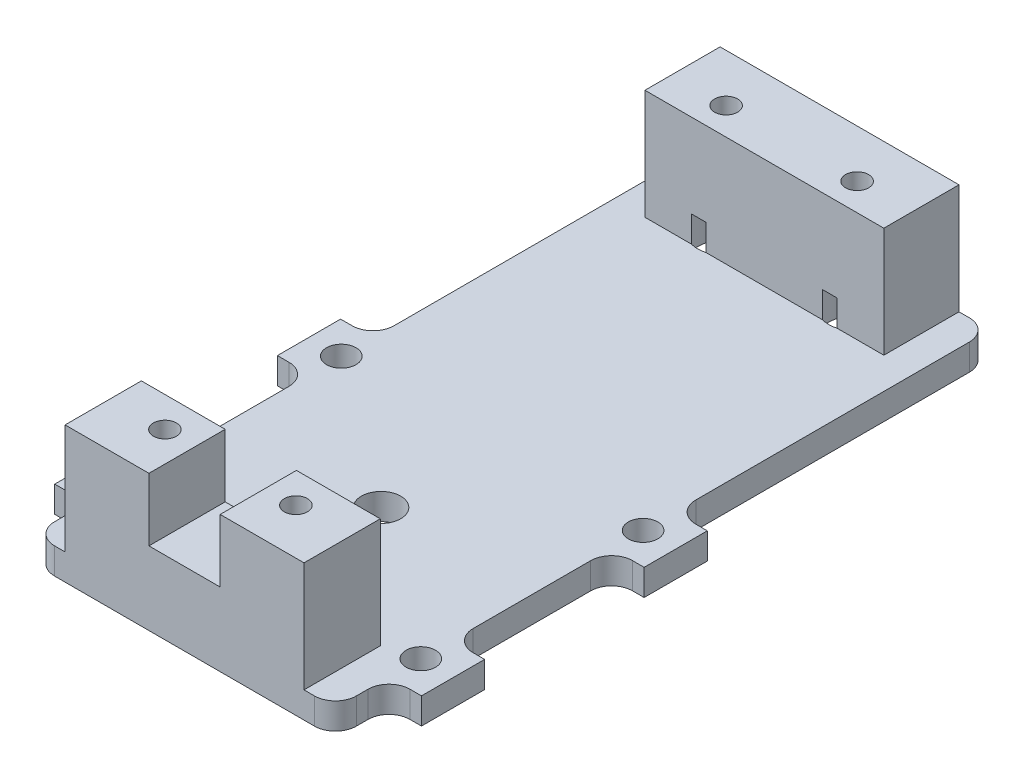
SolidWorks part; units mm, degrees
material "ABS"
ref_plane "Front Plane" through (0, 0, 0) normal (0, 0, 1) x (1, 0, 0)
ref_plane "Top Plane" through (0, 0, 0) normal (0, 1, 0) x (1, 0, 0)
ref_plane "Right Plane" through (0, 0, 0) normal (1, 0, 0) x (0, 0, -1)
sketch "Sketch1" plane through (0, 0, 0) normal (0, 1, 0) x (1, 0, 0)
  line L0 (18.288, -9.6647) -> (22.225, -9.6647)
  line L1 (-18.288, -23.8125) -> (18.288, -23.8125)
  line L2 (-18.288, -23.8125) -> (-18.288, -17.3228)
  line L3 (-18.288, 55.5625) -> (18.288, 55.5625)
  line L4 (18.288, -23.8125) -> (18.288, -17.3228)
  line L5 (-22.225, -17.3228) -> (-18.288, -17.3228)
  line L6 (-22.225, -17.3228) -> (-22.225, -9.6647)
  line L7 (-22.225, 17.3228) -> (-18.288, 17.3228)
  line L8 (22.225, -17.3228) -> (22.225, -9.6647)
  line L9 (0, 0.0043) -> (-31.7584, 0.0043) construction
  line L10 (-31.7584, 0.0043) -> (-18.288, -13.4661) construction
  line L11 (-22.225, -9.6647) -> (-18.288, -9.6647)
  line L12 (-18.288, 17.3228) -> (-18.288, 55.5625)
  line L13 (-22.225, 9.6647) -> (-18.288, 9.6647)
  line L14 (-18.288, -9.6647) -> (-18.288, 9.6647)
  line L15 (18.288, 9.6647) -> (22.225, 9.6647)
  line L17 (18.288, -9.6647) -> (18.288, 9.6647)
  line L18 (22.225, 9.6647) -> (22.225, 17.3228)
  line L19 (-22.225, 9.6647) -> (-22.225, 17.3228)
  line L20 (-18.288, -9.6647) -> (-18.288, 9.6647)
  line L21 (18.288, -9.6647) -> (18.288, 9.6647)
  line L22 (18.288, 17.3228) -> (18.288, 55.5625)
  line L23 (18.288, 17.3228) -> (22.225, 17.3228)
  line L24 (18.288, -17.3228) -> (22.225, -17.3228)
  line L25 (-31.7584, 0.0043) -> (-18.288, 13.4747) construction
  line L26 (0, -23.8125) -> (0, 0.0043) construction
  line L28 (-14.478, -13.8906) -> (14.478, -13.8906) construction
  line L29 (-14.478, -13.8906) -> (-14.478, 45.7994) construction
  line L30 (-14.478, 45.7994) -> (14.478, 45.7994) construction
  line L31 (14.478, -13.8906) -> (14.478, 45.7994) construction
  circle A0 centre (0, 0.0043) radius 2.3813
  circle A1 centre (7.9375, 49.7649) radius 3.429 construction
  circle A2 centre (-7.9375, 49.7649) radius 3.429 construction
  circle A3 centre (7.9375, -18.2563) radius 3.429 construction
  circle A4 centre (-7.9375, -18.2563) radius 3.429 construction
  point P4 (-7.9375, -18.2562)
  point P6 (0, 0)
  point P9 (7.9375, -18.2562)
  point P10 (-7.9375, 49.7649)
  point P11 (7.9375, 49.7649)
  point P31 (18.288, -13.4661)
  point P32 (18.288, 13.4747)
  dimension "D21" = 6.858
  dimension "D1" = 36.576
  dimension "D2" = 79.375
  dimension "D3" = 18.288
  dimension "D4" = 23.8125
  dimension "D5" = 18.2562
  dimension "D6" = 7.9375
  dimension "D9" = 5.5563
  dimension "D10" = 34.6456
  dimension "D11" = 44.45
  dimension "D12" = 19.3294
  dimension "D13" = 9.6647
  dimension "D14" = 19.05
  dimension "D15" = 19.05
  dimension "D16" = 90
  dimension "D17" = 28.956
  dimension "D18" = 14.478
  dimension "D19" = 59.69
  dimension "D20" = 13.8906
  dimension "D7" = 2
  dimension "D8" = 2
extrude "Boss-Extrude1" add sketch "Sketch1" along normal blind 3.175 contours L4 L24 L8 L0 L17 L15 L18 L23 L22 L3 L12 L7 L19 L13 L14 L11 L6 L5 L2 L1 L31 L28 L29 L30 region at (0, 0, -15.3322)
hole_wizard "9/64 (0.14063) Diameter Hole1" positions "Sketch5" profile "Sketch6" hole size "9/64" standard "Ansi Inch" end condition up to next
sketch "Sketch5" plane through (0, 0, 0) normal (0, -1, 0) x (1, 0, 0)
  point P4 (18.288, -13.4747)
  point P7 (18.288, 13.4661)
  point P35 (-18.288, -13.4704)
  point P37 (-18.288, 13.4704)
sketch "Sketch6" plane through (18.288, 0, -13.4747) normal (1, 0, 0) x (0, 0, -1)
  line L0 (0, 0) -> (0, 3.175)
  line L1 (0, 3.175) -> (1.786, 3.175)
  line L2 (1.786, 3.175) -> (1.786, 0)
  line L5 (1.786, 0) -> (0, 0)
  line L11 (0, -6.35) -> (0, 107.95) construction
  dimension "Thru Hole Dia." = 3.572
  dimension "Thru Hole Depth" = 3.175
fillet "Fillet1" radius 2.54 12 edges at (18.288, 1.5875, 23.8125) (18.288, 1.5875, 17.3228) (18.288, 1.5875, 9.6647) (18.288, 1.5875, -9.6647) (18.288, 1.5875, -17.3228) (18.288, 1.5875, -55.5625) (-18.288, 1.5875, -55.5625) (-18.288, 1.5875, -17.3228) (-18.288, 1.5875, -9.6647) (-18.288, 1.5875, 9.6647) (-18.288, 1.5875, 17.3228) (-18.288, 1.5875, 23.8125)
sketch "Sketch9" plane through (0, 0, 0) normal (0, 1, 0) x (1, 0, 0)
  line L0 (-18.288, 55.5625) -> (18.288, 55.5625) construction
  line L1 (-18.288, -23.8125) -> (18.288, -23.8125) construction
  line L5 (-14.478, -14.5696) -> (14.478, -14.5696)
  line L6 (-14.478, -14.5696) -> (-14.478, -23.8125)
  line L8 (-14.4653, 46.453) -> (14.4907, 46.453)
  line L9 (-14.4653, 46.453) -> (-14.4653, 55.5625)
  line L10 (-14.4653, 55.5625) -> (14.4907, 55.5625)
  line L11 (14.4907, 46.453) -> (14.4907, 55.5625)
  line L12 (-14.478, -23.8125) -> (14.478, -23.8125)
  line L13 (14.478, -14.5696) -> (14.478, -23.8125)
  circle A2 centre (-7.9375, -18.2562) radius 1.397
  circle A3 centre (7.9375, -18.2562) radius 1.397
  circle A4 centre (-7.9375, 49.7649) radius 1.397
  circle A5 centre (7.9375, 49.7649) radius 1.397
  dimension "D1" = 2.794
  dimension "D2" = 2.794
  dimension "D3" = 2.794
  dimension "D4" = 2.794
  dimension "D5" = 9.1095
  dimension "D7" = 28.956
  dimension "D8" = 9.2429
extrude "Boss-Extrude3" add sketch "Sketch9" along normal blind 16.51
sketch "Sketch10" plane through (0, 0, 0) normal (0, -1, 0) x (1, 0, 0)
  circle A0 centre (7.9375, 18.2562) radius 3.429
  circle A1 centre (-7.9375, 18.2562) radius 3.429
  circle A2 centre (7.9375, -49.7649) radius 3.429
  circle A3 centre (-7.9375, -49.7649) radius 3.429
extrude "Cut-Extrude1" cut sketch "Sketch10" against normal blind 6.35
sketch "Sketch11" plane through (0, 16.51, 0) normal (0, 1, 0) x (1, 0, 0)
  line L1 (-4.318, -14.5696) -> (4.318, -14.5696)
  line L2 (-4.318, -14.5696) -> (-4.318, -23.8125)
  line L3 (-4.318, -23.8125) -> (4.318, -23.8125)
  line L4 (4.318, -14.5696) -> (4.318, -23.8125)
  line L5 (-14.478, -14.5696) -> (-14.478, -23.8125) construction
  line L6 (14.478, -23.8125) -> (14.478, -14.5696) construction
  point P7 (-14.478, -19.191)
  dimension "D1" = 8.636
  dimension "D2" = 10.16
  dimension "D3" = 10.16
extrude "Cut-Extrude2" cut sketch "Sketch11" against normal blind 7.62
